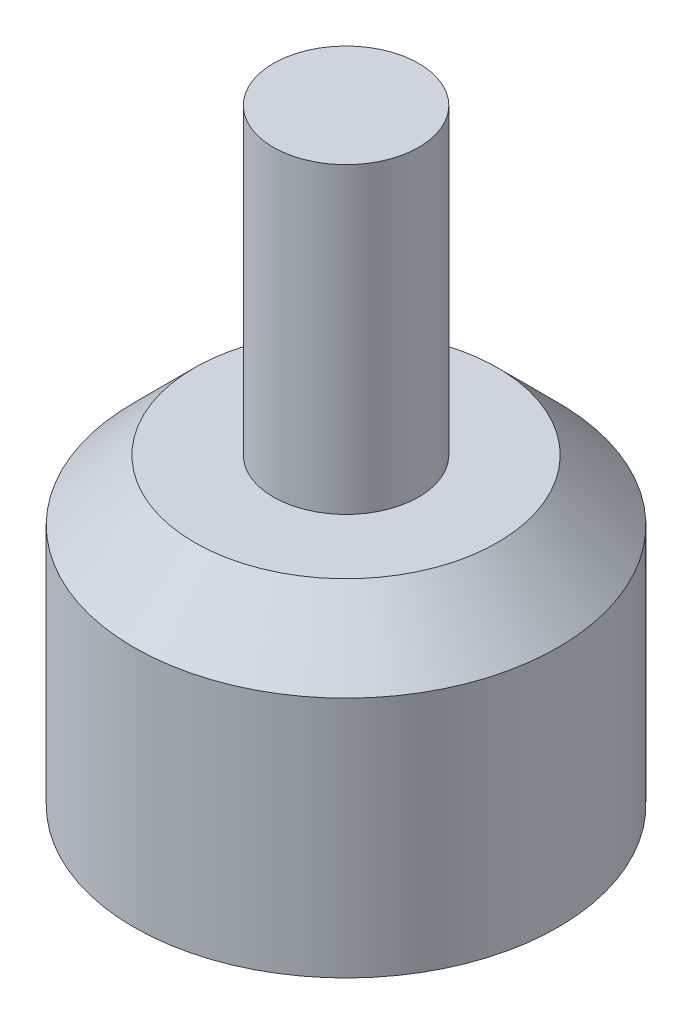
SolidWorks part; units mm, degrees
ref_plane "Front" through (0, 0, 0) normal (0, 0, 1) x (1, 0, 0)
ref_plane "Top" through (0, 0, 0) normal (0, 1, 0) x (1, 0, 0)
ref_plane "Right" through (0, 0, 0) normal (1, 0, 0) x (0, 0, -1)
sketch "Sketch1" plane through (0, 0, 0) normal (0, 1, 0) x (1, 0, 0)
  circle A0 centre (0, 0) radius 7
  dimension "D1" = 14
extrude "Boss-Extrude1" add sketch "Sketch1" along normal blind 10
chamfer "Chamfer1" distance 2 angle 45 1 edges at (0, 10, 7)
sketch "Sketch2" plane through (0, 10, 0) normal (0, 1, 0) x (1, 0, 0)
  circle A0 centre (0, 0) radius 2.4
  dimension "D1" = 4.8
extrude "Boss-Extrude2" add sketch "Sketch2" along normal blind 10
